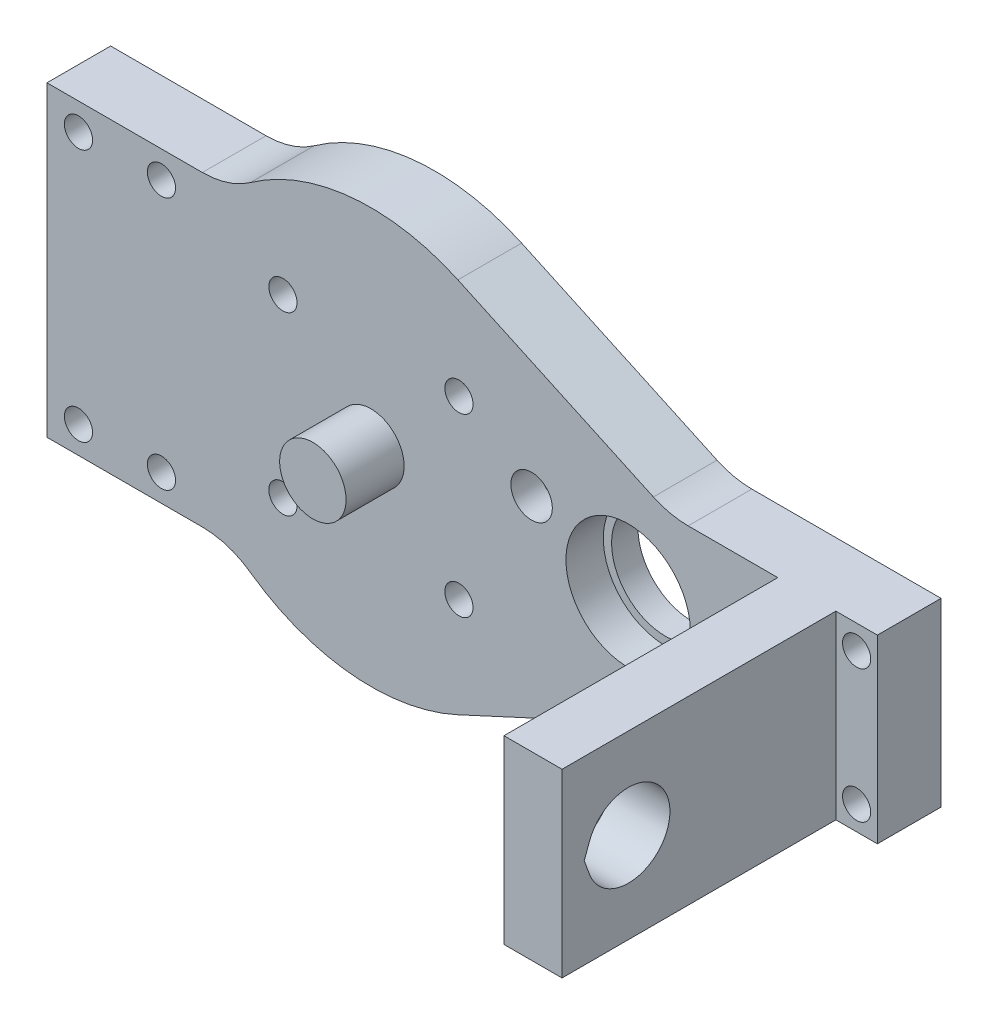
SolidWorks part; units mm, degrees
ref_plane "Front Plane" through (0, 0, 0) normal (0, 0, 1) x (1, 0, 0)
ref_plane "Top Plane" through (0, 0, 0) normal (0, 1, 0) x (1, 0, 0)
ref_plane "Right Plane" through (0, 0, 0) normal (1, 0, 0) x (0, 0, -1)
sketch "Sketch1" plane through (0, 0, 0) normal (0, 0, 1) x (1, 0, 0)
  line L0 (10.4839, 22.6956) -> (36.0323, 10.8939)
  line L1 (36.0323, -10.8939) -> (10.4839, -22.6956)
  circle A0 centre (0, 0) radius 22.215 construction
  circle A1 centre (31, 0) radius 10.2 construction
  arc A2 (10.4839, 22.6956) -> (10.4839, -22.6956) centre (0, 0) ccw
  arc A3 (36.0323, -10.8939) -> (36.0323, 10.8939) centre (31, 0) ccw
  dimension "D1" = 20.4
  dimension "D2" = 44.43
  dimension "D4" = 25
  dimension "D5" = 12
  dimension "D3" = 31
extrude "Boss-Extrude1" add sketch "Sketch1" along normal blind 4.5
sketch "Sketch2" plane through (0, 0, 4.5) normal (0, 0, 1) x (1, 0, 0)
  circle A0 centre (31, 0) radius 7.5
  dimension "D1" = 15
extrude "Cut-Extrude1" cut sketch "Sketch2" against normal through all
sketch "Sketch3" plane through (0, 0, 4.5) normal (0, 0, 1) x (1, 0, 0)
  circle A0 centre (0, 0) radius 4
  dimension "D1" = 8
extrude "Boss-Extrude2" add sketch "Sketch3" along normal blind 7
sketch "Sketch4" plane through (0, 0, 0) normal (0, 0, -1) x (-1, 0, 0)
  line L0 (-36.0323, 10.8939) -> (-56.0323, 10.8939)
  line L1 (-36.0323, -10.8939) -> (-56.0323, -10.8939)
  line L2 (-56.0323, -10.8939) -> (-56.0323, 10.8939)
  line L3 (22.5016, 10.8939) -> (42.5016, 10.8939)
  line L4 (42.5016, 10.8939) -> (42.5016, -10.8939)
  line L5 (42.5016, -10.8939) -> (22.5016, -10.8939)
  arc A0 (-10.4839, -22.6956) -> (-10.4839, 22.6956) centre (0, 0) ccw construction
  arc A1 (22.5016, -10.8939) -> (22.5016, 10.8939) centre (0, 0) ccw
  arc A2 (-36.0323, 10.8939) -> (-36.0323, -10.8939) centre (-31, 0) ccw construction
  arc A3 (-36.0323, 10.8939) -> (-36.0323, -10.8939) centre (-31, 0) ccw
  dimension "D1" = 20
  dimension "D2" = 20
extrude "Boss-Extrude3" add sketch "Sketch4" against normal up to surface (4.5 mm away) up to face at (4, 0, 4.5)
fillet "Fillet1" radius 10 4 edges at (-42.5016, 10.8939, 2.25) (-42.5016, -10.8939, 2.25) (56.0323, -10.8939, 2.25) (56.0323, 10.8939, 2.25)
sketch "Sketch8" plane through (0, 0, 4.5) normal (0, 0, 1) x (1, 0, 0)
  line L0 (56.0323, 0.8939) -> (56.0323, -0.8939) construction
  line L2 (56.0323, 0.8939) -> (56.0323, -0.8939)
  line L3 (55.4014, -4.3896) -> (55.4014, 4.3896)
  line L4 (-42.5016, -0.8939) -> (-42.5016, 0.8939) construction
  line L6 (-42.5016, -0.8939) -> (-42.5016, 0.8939)
  line L7 (-41.8707, 4.3896) -> (-41.8707, -4.3896)
  arc A0 (56.0323, 0.8939) -> (46.0323, 10.8939) centre (46.0323, 0.8939) ccw construction
  arc A1 (46.0323, -10.8939) -> (56.0323, -0.8939) centre (46.0323, -0.8939) ccw construction
  arc A2 (56.0323, 0.8939) -> (55.4014, 4.3896) centre (46.0323, 0.8939) ccw
  arc A3 (55.4014, -4.3896) -> (56.0323, -0.8939) centre (46.0323, -0.8939) ccw
  arc A4 (-32.5016, 10.8939) -> (-42.5016, 0.8939) centre (-32.5016, 0.8939) ccw construction
  arc A5 (-42.5016, -0.8939) -> (-32.5016, -10.8939) centre (-32.5016, -0.8939) ccw construction
  arc A6 (-41.8707, 4.3896) -> (-42.5016, 0.8939) centre (-32.5016, 0.8939) ccw
  arc A7 (-42.5016, -0.8939) -> (-41.8707, -4.3896) centre (-32.5016, -0.8939) ccw
extrude "Cut-Extrude4" cut sketch "Sketch8" against normal through all
sketch "Sketch9" plane through (0, 0, 4.5) normal (0, 0, 1) x (1, 0, 0)
  circle A0 centre (0, 0) radius 15 construction
  circle A1 centre (-10.6066, 10.6066) radius 1
  circle A2 centre (10.6066, 10.6066) radius 1
  circle A3 centre (10.6066, -10.6066) radius 1
  circle A4 centre (-10.6066, -10.6066) radius 1
  point P14 (0, 0)
  dimension "D1" = 30
  dimension "D2" = 2
  dimension "D3" = 4
extrude "Cut-Extrude5" cut sketch "Sketch9" against normal through all
sketch "Sketch10" plane through (0, 0, 4.5) normal (0, 0, 1) x (1, 0, 0)
  circle A0 centre (-10.6066, 10.6066) radius 1.7
  circle A1 centre (10.6066, 10.6066) radius 1.7
  circle A2 centre (10.6066, -10.6066) radius 1.7
  circle A3 centre (-10.6066, -10.6066) radius 1.7
  dimension "D1" = 3.4
extrude "Cut-Extrude6" cut sketch "Sketch10" against normal blind 2.4
sketch "Sketch11" plane through (0, 0, 0) normal (0, 0, -1) x (-1, 0, 0)
  line L0 (-40.9602, 14.6461) -> (-73.6718, 18.9155)
  line L1 (-73.6718, 18.9155) -> (-68.6403, -15.6759)
  line L2 (-68.6403, -15.6759) -> (-41.445, -13.2122)
  arc A0 (-40.9602, 14.6461) -> (-41.445, -13.2122) centre (0, 0) ccw
  dimension "D1" = 87
extrude "Cut-Extrude7" cut sketch "Sketch11" against normal up to surface (4.5 mm away) up to face at (-8.9066, -10.6066, 4.5)
fillet "Fillet2" radius 10 2 edges at (42.1138, -10.8939, 2.25) (42.1138, 10.8939, 2.25)
sketch "Sketch12" plane through (0, 0, 4.5) normal (0, 0, 1) x (1, 0, 0)
  line L0 (-22.5016, 10.8939) -> (-42.5927, 14.8195)
  line L1 (-42.5927, 14.8195) -> (-48.1481, -13.6126)
  line L2 (-48.1481, -13.6126) -> (-27.4273, -14.3153)
  line L3 (-27.4273, -14.3153) -> (-22.5016, -10.8939)
  arc A0 (-22.5016, 10.8939) -> (-22.5016, -10.8939) centre (0, 0) ccw
extrude "Cut-Extrude8" cut sketch "Sketch12" against normal through all
sketch "Sketch23" plane through (0, 0, 0) normal (0, 0, -1) x (-1, 0, 0)
  line L2 (-36.0323, -10.8939) -> (-10.4839, -22.6956)
  line L3 (-10.4839, 22.6956) -> (-36.0323, 10.8939)
  line L4 (-36.0323, -10.8939) -> (-10.4839, -22.6956)
  line L5 (-10.4839, 22.6956) -> (-36.0323, 10.8939)
  circle A0 centre (-10.6066, -10.6066) radius 1 construction
  circle A1 centre (10.6066, -10.6066) radius 1 construction
  circle A2 centre (10.6066, 10.6066) radius 1 construction
  circle A3 centre (-10.6066, 10.6066) radius 1 construction
  arc A4 (-10.4839, -22.6956) -> (-10.4839, 22.6956) centre (0, 0) ccw
  arc A5 (-36.0323, 10.8939) -> (-43.4709, 1.5916) centre (-33.4776, 1.2257) ccw
  arc A6 (-43.4709, 1.5916) -> (-43.4709, -1.5916) centre (0, 0) ccw
  arc A7 (-43.4709, -1.5916) -> (-36.0323, -10.8939) centre (-33.4776, -1.2257) ccw
  arc A8 (-10.4839, -22.6956) -> (-10.4839, 22.6956) centre (0, 0) ccw
  arc A9 (-36.0323, 10.8939) -> (-43.4709, 1.5916) centre (-33.4776, 1.2257) ccw
  arc A10 (-43.4709, 1.5916) -> (-43.4709, -1.5916) centre (0, 0) ccw
  arc A11 (-43.4709, -1.5916) -> (-36.0323, -10.8939) centre (-33.4776, -1.2257) ccw
  circle A12 centre (-10.6066, -10.6066) radius 1
  circle A13 centre (10.6066, -10.6066) radius 1
  circle A14 centre (10.6066, 10.6066) radius 1
  circle A15 centre (-10.6066, 10.6066) radius 1
  circle A16 centre (-31, 0) radius 6.5
  dimension "D2" = 13
  dimension "D1" = 0
extrude "Boss-Extrude6" add sketch "Sketch23" along normal blind 3.175
sketch "Sketch24" plane through (0, 0, -3.175) normal (0, 0, -1) x (-1, 0, 0)
  line L0 (-10.6066, 10.6066) -> (10.6066, 10.6066) construction
ref_axis "Axis1" through (10.6066, 10.6066, -3.175) along (-1, 0, 0)
sketch "Sketch25" plane through (0, 0, -3.175) normal (0, 0, -1) x (-1, 0, 0)
  line L1 (-36.0323, 10.8939) -> (-56.0323, 10.8939)
  line L3 (-36.0323, -10.8939) -> (-56.0323, -10.8939)
  line L4 (-56.0323, 10.8939) -> (-56.0323, -10.8939)
  arc A0 (-43.4709, -1.5916) -> (-36.0323, -10.8939) centre (-33.4776, -1.2257) ccw construction
  arc A1 (-43.4709, 1.5916) -> (-43.4709, -1.5916) centre (0, 0) ccw construction
  arc A2 (-36.0323, 10.8939) -> (-43.4709, 1.5916) centre (-33.4776, 1.2257) ccw construction
  arc A3 (-43.4709, -1.5916) -> (-36.0323, -10.8939) centre (-33.4776, -1.2257) ccw
  arc A4 (-43.4709, 1.5916) -> (-43.4709, -1.5916) centre (0, 0) ccw
  arc A5 (-36.0323, 10.8939) -> (-43.4709, 1.5916) centre (-33.4776, 1.2257) ccw
  dimension "D1" = 20
extrude "Boss-Extrude7" add sketch "Sketch25" against normal up to surface (7.675 mm away) up to face at (24.5985, 0, 4.5)
sketch "Sketch26" plane through (0, 0, 4.5) normal (0, 0, 1) x (1, 0, 0)
  line L0 (36.0323, 10.8939) -> (56.0323, 10.8939) construction
  line L1 (56.0323, -10.8939) -> (47.0323, -10.8939)
  line L2 (56.0323, -10.8939) -> (56.0323, 10.8939)
  line L3 (56.0323, 10.8939) -> (47.0323, 10.8939)
  line L4 (47.0323, -10.8939) -> (47.0323, 10.8939)
  dimension "D1" = 9
extrude "Boss-Extrude8" add sketch "Sketch26" along normal blind 33
sketch "Sketch27" plane through (56.0323, 0, 0) normal (1, 0, 0) x (0, 0, -1)
  circle A0 centre (-29.5, 0) radius 5
extrude "Cut-Extrude9" cut sketch "Sketch27" against normal up to next
sketch "Sketch28" plane through (0, 0, -3.175) normal (0, 0, -1) x (-1, 0, 0)
  line L1 (16.8152, 18.5) -> (50.7321, 18.5)
  line L3 (16.8152, -18.5) -> (50.7321, -18.5)
  line L4 (0, 0) -> (54, 0) construction
  line L5 (54, 0) -> (25.875, 18.5) construction
  line L6 (54, 0) -> (31.6196, -18.5) construction
  line L7 (50.7321, -18.5) -> (25, 0) construction
  line L8 (25, 0) -> (50.7321, 18.5) construction
  line L9 (50.7321, 18.5) -> (50.7321, -18.5)
  arc A0 (50.7321, -18.5) -> (50.7321, 18.5) centre (0, 0) ccw construction
  arc A2 (-10.4839, -22.6956) -> (-10.4839, 22.6956) centre (0, 0) ccw construction
  arc A3 (16.8152, -18.5) -> (16.8152, 18.5) centre (0, 0) ccw
  dimension "D1" = 108
  dimension "D3" = 37
extrude "Boss-Extrude9" add sketch "Sketch28" against normal up to surface (7.675 mm away) up to face at (38.5, 0, 4.5)
sketch "Sketch29" plane through (0, 0, 4.5) normal (0, 0, 1) x (1, 0, 0)
  line L0 (-50.7321, 18.5) -> (-33.7737, 18.5)
  line L1 (-50.7321, 18.5) -> (-50.7321, -18.5)
  line L2 (-50.7321, -18.5) -> (-33.7737, -18.5)
  line L3 (-16.8152, -18.5) -> (-50.7321, -18.5) construction
  line L4 (-50.7321, 18.5) -> (-16.8152, 18.5) construction
  line L5 (-48.7321, 16.5) -> (-48.7321, -16.5)
  line L6 (-48.7321, 16.5) -> (-50.7321, 18.5) construction
  line L7 (-48.7321, -16.5) -> (-50.7321, -18.5) construction
  line L8 (-48.7321, 16.5) -> (-33.7737, 16.5)
  line L9 (-33.7737, 16.5) -> (-33.7737, 18.5)
  line L10 (-33.7737, -18.5) -> (-33.7737, -16.5)
  line L11 (-33.7737, -16.5) -> (-48.7321, -16.5)
  dimension "D1" = 33
  dimension "D2" = 2
extrude "Boss-Extrude10" add sketch "Sketch29" along normal blind 105
fillet "Fillet4" radius 10 4 edges at (36.0323, 10.8939, 0.6625) (36.0323, -10.8939, 0.6625) (-16.8152, 18.5, 0.6625) (-16.8152, -18.5, 0.6625)
sketch "Sketch30" plane through (56.0323, 0, 0) normal (1, 0, 0) x (0, 0, -1)
  line L0 (-34.1928, 1.7255) -> (-34.8273, 0)
  line L1 (-34.8273, 0) -> (-34.1928, -1.7255)
  line L2 (-34.5, 0) -> (-34.8273, 0) construction
  circle A0 centre (-29.5, 0) radius 5 construction
  arc A1 (-34.1928, 1.7255) -> (-34.1928, -1.7255) centre (-29.5, 0) ccw
extrude "Cut-Extrude10" cut sketch "Sketch30" against normal up to surface (9 mm away) up to face at (47.0323, 0, 24.5)
sketch "Sketch31" plane through (0, 0, 4.5) normal (0, 0, 1) x (1, 0, 0)
  line L0 (-46.6706, 12.5) -> (-48.7321, 16.5) construction
  line L1 (-46.6706, 12.5) -> (-34.6706, 12.5)
  line L2 (-46.6706, 12.5) -> (-46.6706, -12.5)
  line L3 (-46.6706, -12.5) -> (-34.6706, -12.5)
  line L4 (-34.6706, 12.5) -> (-34.6706, -12.5)
  line L5 (-46.6706, -12.5) -> (-48.7321, -16.5) construction
  dimension "D1" = 25
  dimension "D2" = 12
  dimension "D3" = 4.5
extrude "Cut-Extrude11" cut sketch "Sketch31" against normal through all
sketch "Sketch32" plane through (0, 0, 4.5) normal (0, 0, 1) x (1, 0, 0)
  line L0 (-33.7737, 18.5) -> (-33.7737, 16.5)
  line L1 (-33.7737, 16.5) -> (-27.7321, 16.5)
  line L2 (-27.7321, 16.5) -> (-27.7321, -16.5)
  line L3 (-27.7321, -16.5) -> (-33.7737, -16.5)
  line L4 (-33.7737, -16.5) -> (-33.7737, -18.5)
  line L5 (-33.7737, -18.5) -> (-27.045, -18.5)
  line L6 (-20.3162, -18.5) -> (-33.7737, -18.5) construction
  line L7 (-27.045, -18.5) -> (-27.045, 18.5)
  line L8 (-33.7737, 18.5) -> (-20.3162, 18.5) construction
  line L9 (-27.045, 18.5) -> (-33.7737, 18.5)
extrude "Boss-Extrude11" add sketch "Sketch32" along normal blind 10
sketch "Sketch33" plane through (-27.045, 0, 0) normal (1, 0, 0) x (0, 0, -1)
  line L0 (-4.5, -22.6956) -> (-4.5, -11.8156) construction
  line L1 (-14.5, 16.5) -> (-4.5, 16.5)
  line L2 (-14.5, 16.5) -> (-14.5, -16.5)
  line L3 (-14.5, -16.5) -> (-4.5, -16.5)
  line L4 (-4.5, 16.5) -> (-4.5, -16.5)
  line L5 (-109.5, -16.5) -> (-4.5, -16.5) construction
extrude "Cut-Extrude12" cut sketch "Sketch33" against normal up to next
sketch "Sketch34" plane through (-48.7321, 0, 0) normal (1, 0, 0) x (0, 0, -1)
  line L0 (-109.5, 16.5) -> (-109.5, 18.5) construction
  line L1 (-109.5, 17.5) -> (-4.5, 17.5)
  line L2 (-109.5, 17.5) -> (-109.5, -17.5)
  line L3 (-109.5, -17.5) -> (-4.5, -17.5)
  line L4 (-4.5, 17.5) -> (-4.5, -17.5)
  line L5 (-4.5, -18.5) -> (-4.5, -16.5) construction
extrude "Cut-Extrude13" cut sketch "Sketch34" along normal up to surface (21.6872 mm away) up to face at (-27.045, -17.5, 9.5)
sketch "Sketch35" plane through (56.0323, 0, 0) normal (1, 0, 0) x (0, 0, -1)
  circle A0 centre (-29.5, 0) radius 5.5
  dimension "D1" = 11
extrude "Cut-Extrude14" [suppressed] cut sketch "Sketch35" against normal up to next
sketch "Sketch36" [suppressed] plane through (56.0323, 0, 0) normal (1, 0, 0) x (0, 0, -1)
  line L0 (-34.3284, 2.6337) -> (-35.765, 0)
  line L1 (-35.765, 0) -> (-34.3284, -2.6337)
  line L2 (-35.765, 0) -> (0, 0) construction
  circle A0 centre (-29.5, 0) radius 5.5 construction
  arc A1 (-34.3284, -2.6337) -> (-34.3284, 2.6337) centre (-29.5, 0) cw
  dimension "D1" = 3
extrude "Cut-Extrude15" [suppressed] cut sketch "Sketch36" against normal up to next
sketch "Sketch37" plane through (0, 0, 37.5) normal (0, 0, 1) x (1, 0, 0)
  line L0 (47.0323, -10.8939) -> (56.0323, -10.8939) construction
  line L1 (47.0323, 10.8939) -> (49.0323, 10.8939)
  line L2 (47.0323, 10.8939) -> (47.0323, -10.8939)
  line L3 (47.0323, -10.8939) -> (49.0323, -10.8939)
  line L4 (49.0323, 10.8939) -> (49.0323, -10.8939)
  dimension "D1" = 2
extrude "Cut-Extrude16" cut sketch "Sketch37" against normal up to surface (33 mm away) up to face at (-0.8985, 0, 4.5)
sketch "Sketch38" plane through (0, 0, 4.5) normal (0, 0, 1) x (1, 0, 0)
  line L0 (19.3604, 4.5575) -> (42.6396, -4.5575) construction
  circle A0 centre (31, 0) radius 12.5 construction
  circle A1 centre (19.3604, 4.5575) radius 1.5
  circle A2 centre (42.6396, -4.5575) radius 1.5
  dimension "D1" = 25
  dimension "D2" = 3
extrude "Cut-Extrude17" cut sketch "Sketch38" against normal blind 10
sketch "Sketch39" plane through (0, 0, 4.5) normal (0, 0, 1) x (1, 0, 0)
  circle A0 centre (19.3604, 4.5575) radius 2.5
  circle A1 centre (42.6396, -4.5575) radius 2.5
  dimension "D1" = 5
extrude "Cut-Extrude18" cut sketch "Sketch39" against normal blind 3.5
sketch "Sketch40" plane through (0, 0, 4.5) normal (0, 0, 1) x (1, 0, 0)
  line L1 (-50.7321, 18.5) -> (-27.045, 18.5)
  line L2 (-50.7321, 18.5) -> (-50.7321, -18.5)
  line L3 (-50.7321, -18.5) -> (-27.045, -18.5)
  line L4 (-27.045, 18.5) -> (-27.045, -18.5)
extrude "Cut-Extrude19" cut sketch "Sketch40" along normal blind 133.5
sketch "Sketch41" plane through (0, 0, 4.5) normal (0, 0, 1) x (1, 0, 0)
  line L1 (-46.6706, 12.5) -> (-34.6706, 12.5)
  line L2 (-46.6706, 12.5) -> (-46.6706, -12.5)
  line L3 (-46.6706, -12.5) -> (-34.6706, -12.5)
  line L4 (-34.6706, 12.5) -> (-34.6706, -12.5)
extrude "Boss-Extrude12" add sketch "Sketch41" against normal up to surface (7.675 mm away) up to face at (17.8604, 4.5575, -3.175)
sketch "Sketch42" plane through (0, 0, 4.5) normal (0, 0, 1) x (1, 0, 0)
  line L0 (-20.3162, -18.5) -> (-50.7321, -18.5) construction
  line L1 (-50.7321, 18.5) -> (-39.0453, 18.5)
  line L2 (-50.7321, 18.5) -> (-50.7321, -18.5)
  line L3 (-50.7321, -18.5) -> (-39.0453, -18.5)
  line L4 (-39.0453, 18.5) -> (-39.0453, -18.5)
extrude "Cut-Extrude20" cut sketch "Sketch42" against normal through all
sketch "Sketch43" plane through (0, 0, 4.5) normal (0, 0, 1) x (1, 0, 0)
  line L0 (-39.0453, 18.5) -> (-35.2453, 15.2504) construction
  line L1 (-35.2453, 15.2504) -> (-25.2453, 15.2504) construction
  line L2 (-35.2453, 15.2504) -> (-35.2453, -15.2504) construction
  line L3 (-35.2453, -15.2504) -> (-25.2453, -15.2504) construction
  line L4 (-25.2453, 15.2504) -> (-25.2453, -15.2504) construction
  line L5 (-35.2453, -15.2504) -> (-39.0453, -18.5) construction
  line L7 (-39.0453, -18.5) -> (-39.0453, 18.5) construction
  circle A0 centre (-35.2453, 15.2504) radius 1
  circle A1 centre (-35.2453, -15.2504) radius 1
  circle A2 centre (-25.2453, 15.2504) radius 1
  circle A3 centre (-25.2453, -15.2504) radius 1
  point P10 (-35.7475, 14.7418)
  point P12 (-35.2217, 15.2782)
  dimension "D1" = 2
  dimension "D2" = 5
  dimension "D3" = 10
  dimension "D4" = 3.8
extrude "Cut-Extrude21" cut sketch "Sketch43" against normal through all
sketch "Sketch44" plane through (0, 0, 4.5) normal (0, 0, 1) x (1, 0, 0)
  circle A0 centre (-35.2453, 15.2504) radius 1.7
  circle A1 centre (-25.2453, 15.2504) radius 1.7
  circle A2 centre (-35.2453, -15.2504) radius 1.7
  circle A3 centre (-25.2453, -15.2504) radius 1.7
  circle A4 centre (-10.6066, 10.6066) radius 1.7 construction
extrude "Cut-Extrude22" cut sketch "Sketch44" against normal blind 3
sketch "Sketch45" plane through (0, 0, -3.175) normal (0, 0, -1) x (-1, 0, 0)
  line L0 (-56.0323, -10.8939) -> (-38.2303, -10.8939) construction
  line L1 (-56.0323, 10.8939) -> (-61.0323, 10.8939)
  line L2 (-56.0323, 10.8939) -> (-56.0323, -10.8939)
  line L3 (-56.0323, -10.8939) -> (-61.0323, -10.8939)
  line L4 (-61.0323, 10.8939) -> (-61.0323, -10.8939)
  line L5 (-61.0323, 10.8939) -> (-58.5323, 8) construction
  line L6 (-58.5323, 8) -> (-58.5323, -8) construction
  line L7 (-58.5323, -8) -> (-61.0323, -10.8939) construction
  line L8 (-58.5323, -8) -> (-56.0323, -10.8939) construction
  circle A0 centre (-58.5323, 8) radius 1
  circle A1 centre (-58.5323, -8) radius 1
  dimension "D3" = 2
  dimension "D1" = 5
  dimension "D2" = 16
extrude "Boss-Extrude13" add sketch "Sketch45" against normal up to surface (7.675 mm away) up to face at (-23.5453, 15.2504, 4.5)
sketch "Sketch46" plane through (0, 0, 4.5) normal (0, 0, 1) x (1, 0, 0)
  circle A0 centre (58.5323, 8) radius 1.7
  circle A1 centre (58.5323, -8) radius 1.7
  circle A2 centre (10.6066, -10.6066) radius 1.7 construction
extrude "Cut-Extrude23" cut sketch "Sketch46" against normal blind 3
